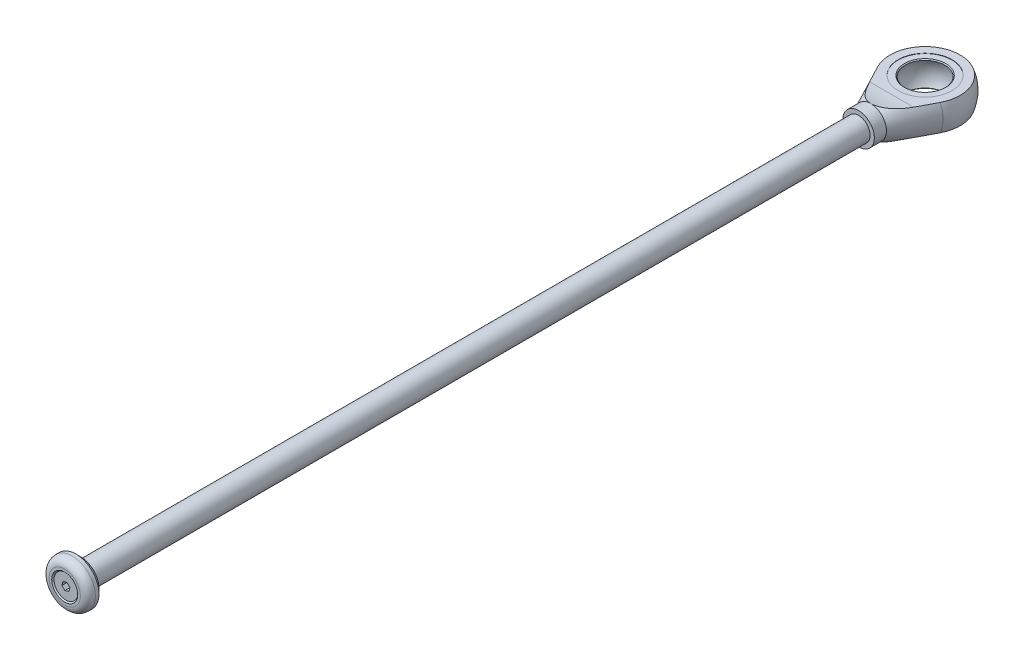
SolidWorks part; units mm, degrees
ref_plane "Front Plane" through (0, 0, 0) normal (0, 0, 1) x (1, 0, 0)
ref_plane "Top Plane" through (0, 0, 0) normal (0, 1, 0) x (1, 0, 0)
ref_plane "Right Plane" through (0, 0, 0) normal (1, 0, 0) x (0, 0, -1)
sketch "Sketch1" plane through (0, 0, 0) normal (0, 1, 0) x (1, 0, 0)
  line L0 (0, 0) -> (0, -339.448) construction
  line L1 (-11.7122, -5.525) -> (-5.45, -18.8)
  line L2 (-5.45, -18.8) -> (-5.45, -23)
  line L3 (-5.45, -23) -> (-4, -23)
  line L4 (-4, -23) -> (-4, -292)
  line L5 (0, 12.95) -> (0, 8)
  line L6 (-4, -292) -> (-6.35, -292)
  line L7 (-6.35, -292) -> (-8, -293.65)
  line L8 (-8, -293.65) -> (-8, -294.9)
  line L9 (-5.4, -297.5) -> (-4.5, -297.5)
  line L10 (-4.5, -297.5) -> (-4.1, -297.1)
  line L11 (-4.1, -297.1) -> (0, -297.1)
  line L12 (0, -297.1) -> (0, -8)
  arc A0 (0, 12.95) -> (-11.7122, -5.525) centre (0, 0) ccw
  arc A1 (0, 8) -> (0, -8) centre (0, 0) ccw
  arc A2 (-8, -294.9) -> (-5.4, -297.5) centre (-5.4, -294.9) ccw
  dimension "D1" = 25.9
  dimension "D6" = 16
  dimension "D2" = 10.9
  dimension "D3" = 8
  dimension "D4" = 23
  dimension "D5" = 4.2
  dimension "D7" = 269
  dimension "D8" = 16
  dimension "D9" = 12.7
  dimension "D10" = 45
  dimension "D11" = 5.5
  dimension "D12" = 9
  dimension "D13" = 0.4
  dimension "D14" = 1.25
revolve "Revolve1" add sketch "Sketch1" angle 360 about L0
sketch "Sketch2" plane through (0, 0, 297.1) normal (0, 0, 1) x (1, 0, 0)
  line L1 (1.3867, 0.4004) -> (0.3466, 1.4011)
  line L2 (0.3466, 1.4011) -> (-1.0401, 1.0007)
  line L3 (-1.0401, 1.0007) -> (-1.3867, -0.4004)
  line L4 (-1.3867, -0.4004) -> (-0.3466, -1.4011)
  line L5 (-0.3466, -1.4011) -> (1.0401, -1.0007)
  line L6 (1.0401, -1.0007) -> (1.3867, 0.4004)
  circle A0 centre (0, 0) radius 1.25 construction
  dimension "D1" = 2.5
extrude "Extrude1" cut sketch "Sketch2" against normal blind 2
sketch "Sketch3" plane through (0, 0, 0) normal (1, 0, 0) x (0, 0, -1)
  line L0 (18.704, 4.55) -> (-11.6, 4.55)
  line L1 (-23, 5.45) -> (-18.8, 5.45)
  line L2 (-18.8, 5.45) -> (-23, 5.45) construction
  line L3 (0, 0) -> (19.5476, 0) construction
  line L4 (-23, 5.45) -> (-23, 17.7314)
  line L5 (-23, 17.7314) -> (18.704, 17.7314)
  line L6 (18.704, 17.7314) -> (18.704, 4.55)
  line L7 (-23, 4) -> (-23, -4) construction
  line L8 (18.704, -17.7314) -> (18.704, -4.55)
  line L9 (-23, -17.7314) -> (18.704, -17.7314)
  line L10 (-23, -5.45) -> (-23, -17.7314)
  line L11 (-23, -5.45) -> (-18.8, -5.45)
  line L12 (18.704, -4.55) -> (-11.6, -4.55)
  arc A0 (-11.6, 4.55) -> (-18.8, 5.45) centre (-11.6, 33.8) cw
  arc A1 (-11.6, -4.55) -> (-18.8, -5.45) centre (-11.6, -33.8) ccw
  dimension "D1" = 9.1
  dimension "D2" = 11.4
extrude "Extrude2" cut sketch "Sketch3" against normal through all and the other way through all
sketch "Sketch4" plane through (0, 4.55, 0) normal (0, 1, 0) x (1, 0, 0)
  circle A0 centre (0, 0) radius 9.3
  dimension "D1" = 18.6
extrude "Extrude3" cut sketch "Sketch4" against normal blind 0.1
mirror "Mirror1" about plane through (0, 0, 0) normal (0, 1, 0) of "Extrude3"
chamfer "Chamfer1" distance 0.5 angle 45 2 edges at (0, -4.45, -6.6481) (0, 4.45, 6.6481) first distance on face at (0, -4.45, -6.6481) first distance on face at (0, 4.45, 6.6481)
